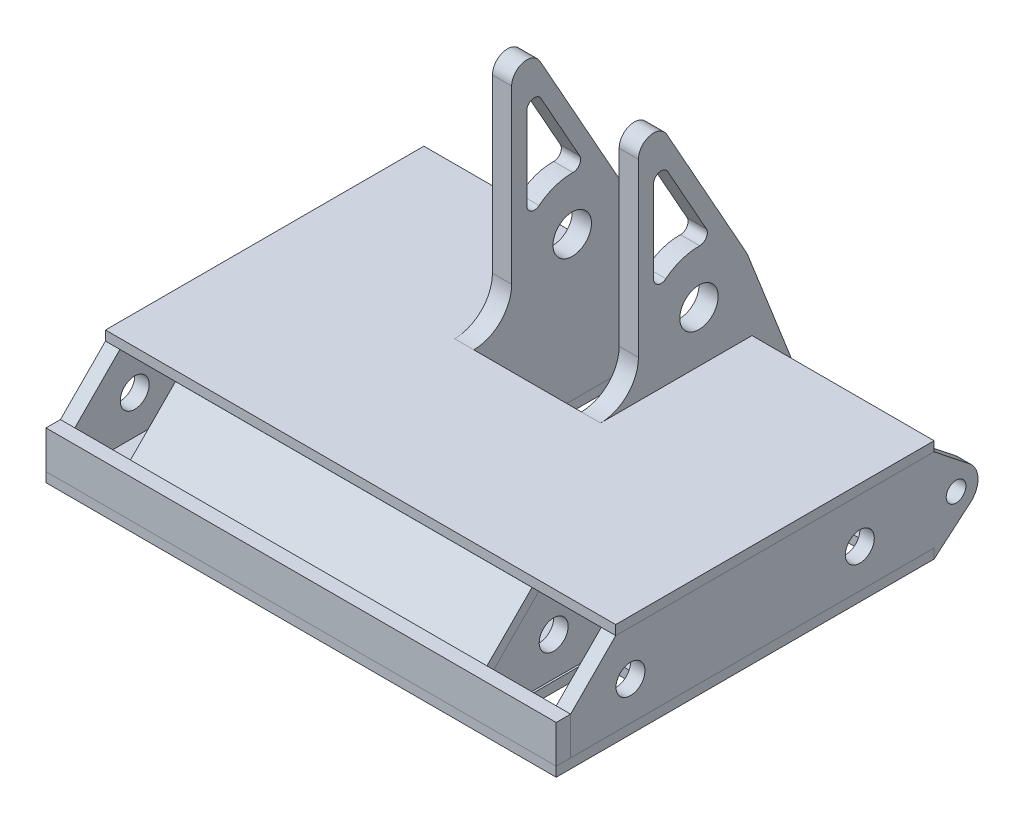
SolidWorks part; units mm, degrees
material "2024-T4"
ref_plane "Front Plane" through (0, 0, 0) normal (0, 0, 1) x (1, 0, 0)
ref_plane "Top Plane" through (0, 0, 0) normal (0, 1, 0) x (1, 0, 0)
ref_plane "Right Plane" through (0, 0, 0) normal (1, 0, 0) x (0, 0, -1)
sketch "Side View" plane through (0, 0, 0) normal (1, 0, 0) x (0, 0, -1)
  line L1 (165, 199.6593) -> (165, 86.35)
  line L3 (140, 55) -> (29.7536, 55)
  line L4 (240, 0) -> (240, 55) construction
  line L5 (0, 0) -> (240, 0)
  line L9 (183.7233, 204.5484) -> (235.5315, 112.1122)
  line L10 (179.9201, 117.2092) -> (110.2141, 38.4935) construction
  line L11 (29.7536, 55) -> (140, 55)
  line L12 (29.7536, 55) -> (29.7536, 61.35) construction
  line L13 (29.7536, 61.35) -> (140, 61.35) construction
  line L14 (140, 55) -> (140, 61.35)
  line L15 (0, 0) -> (240, 0) construction
  line L16 (0, 0) -> (0, -6.35) construction
  line L17 (0, -6.35) -> (240, -6.35) construction
  line L18 (240, 0) -> (240, -6.35) construction
  line L19 (223.5253, 67.0883) -> (135.9217, 8.9446) construction
  line L20 (240, 55) -> (240, 0) construction
  line L21 (240, 0) -> (240, -6.35)
  line L22 (240, 55) -> (230.475, 55) construction
  line L23 (230.475, 55) -> (230.475, 0) construction
  line L24 (13.588, 51.1116) -> (-9.525, 27.8072) construction
  line L25 (240, -6.35) -> (263.8895, 13.9507)
  line L26 (267.9974, 30.2982) -> (237.5799, 107.7886)
  line L27 (13.588, 51.1116) -> (167.8998, 206.7011) construction
  line L28 (190.9625, 41.565) -> (39.5125, 41.565) construction
  line L29 (39.5125, 25.4) -> (190.9625, 25.4) construction
  line L30 (190.9625, 9.235) -> (39.5125, 9.235) construction
  line L31 (-9.525, 25) -> (-9.525, -6.35) construction
  line L32 (-9.525, -6.35) -> (0, -6.35) construction
  line L33 (0, 0) -> (0, 25)
  line L34 (0, 25) -> (29.7536, 55)
  line L35 (-9.525, 25) -> (0, 25) construction
  line L36 (-4.5086, 29.4716) -> (25.245, 59.4716) construction
  line L37 (0, 25) -> (-4.5086, 29.4716) construction
  line L38 (29.7536, 55) -> (25.245, 59.4716) construction
  line L39 (39.701, -11.1125) -> (190.9636, -11.1125) construction
  circle A1 centre (205, 95) radius 12.7
  circle A2 centre (205, 95) radius 100 construction
  arc A3 (183.7233, 204.5484) -> (165, 199.6593) centre (175, 199.6593) ccw
  arc A4 (140, 61.35) -> (165, 86.35) centre (140, 86.35) ccw
  circle A5 centre (125, 25.4) radius 19.75 construction
  circle A6 centre (205, 95) radius 33.5 construction
  circle A7 centre (39.5125, 25.4) radius 36.5125 construction
  circle A8 centre (190.9625, 25.4) radius 36.5125 construction
  circle A9 centre (254.5, 25) radius 6.5
  arc A11 (263.8895, 13.9507) -> (267.9974, 30.2982) centre (254.5, 25) ccw
  arc A13 (237.5799, 107.7886) -> (235.5315, 112.1122) centre (205, 95) ccw
  circle A14 centre (190.9625, 25.4) radius 16.165 construction
  circle A15 centre (39.5125, 25.4) radius 16.165 construction
  point P16 (240, 0)
  point P24 (165, 237.9546)
  point P40 (217.1923, 0)
  point P45 (164.7327, 0)
  point P49 (65.7423, 0)
  point P50 (13.2827, 0)
  dimension "D1" = 25.4
  dimension "D3" = 200
  dimension "D8" = 10
  dimension "D11" = 39.5
  dimension "D15" = 67
  dimension "D17" = 73.025
  dimension "D16" = 13
  dimension "D29" = 73.025
  dimension "D31" = 32.33
  dimension "D32" = 32.33
  dimension "D28" = 35
  dimension "D2" = 55
  dimension "D9" = 6.35
  dimension "D10" = 25
  dimension "D14" = 40
  dimension "D5" = 5
  dimension "D4" = 35
  dimension "D18" = 4.7625
  dimension "D7" = 5
  dimension "D20" = 3
  dimension "D22" = 25
  dimension "D26" = 9.525
  dimension "D13" = 80
  dimension "D19" = 3
  dimension "D6" = 240
  dimension "D24" = 8
  dimension "D25" = 8
  dimension "D27" = 25
  dimension "D30" = 4.7625
  dimension "D34" = 151.45
  dimension "D21" = 6.35
sketch "Top View" plane through (0, 0, 0) normal (0, 1, 0) x (1, 0, 0)
  line L0 (0, 120) -> (0, 0) construction
  line L1 (168.45, 0) -> (158.925, 0)
  line L2 (168.45, 0) -> (168.45, 240)
  line L3 (168.45, 240) -> (35.5, 240)
  line L4 (-168.45, 0) -> (-168.45, 240)
  line L5 (168.45, 0) -> (-168.45, 240) construction
  line L6 (168.45, 240) -> (-168.45, 0) construction
  line L9 (-35.5, 240) -> (-35.5, 0)
  line L11 (35.5, 240) -> (35.5, 0)
  line L13 (-158.925, 230.475) -> (-158.925, 0)
  line L15 (-117.725, 230.475) -> (-117.725, 0)
  line L17 (158.925, 230.475) -> (117.725, 230.475)
  line L18 (158.925, 230.475) -> (158.925, 0)
  line L19 (-35.5, 240) -> (-168.45, 240)
  line L20 (-158.925, 0) -> (-168.45, 0)
  line L22 (158.925, 230.475) -> (48.2, 230.475)
  line L26 (-48.2, 230.475) -> (-158.925, 230.475)
  line L29 (158.925, 0) -> (-108.2, 0)
  line L33 (-131.175, 190.9625) -> (-131.175, 229.0625) construction
  line L35 (-141.335, 77.6125) -> (-141.335, 1.4125) construction
  line L36 (108.2, 165.9625) -> (58.2, 165.9625) construction
  line L37 (-108.2, 215.9625) -> (-58.2, 215.9625) construction
  line L38 (-108.2, 215.9625) -> (-108.2, 165.9625) construction
  line L39 (-108.2, 165.9625) -> (-58.2, 165.9625) construction
  line L40 (-58.2, 215.9625) -> (-58.2, 165.9625) construction
  line L41 (58.2, 215.9625) -> (58.2, 165.9625) construction
  line L42 (108.2, 215.9625) -> (58.2, 215.9625) construction
  line L43 (108.2, 215.9625) -> (108.2, 165.9625) construction
  line L45 (-141.335, 229.0625) -> (-121.015, 229.0625) construction
  line L46 (-141.335, 229.0625) -> (-141.335, 152.8625) construction
  line L47 (-141.335, 152.8625) -> (-121.015, 152.8625) construction
  line L49 (-141.335, 229.0625) -> (-121.015, 152.8625) construction
  line L50 (-141.335, 152.8625) -> (-121.015, 229.0625) construction
  line L54 (-108.2, 240) -> (-108.2, 0) construction
  line L56 (-121.015, 77.6125) -> (-121.015, 1.4125) construction
  line L57 (-48.2, 230.475) -> (-48.2, 0)
  line L58 (48.2, 230.475) -> (48.2, 0)
  line L59 (-108.2, 0) -> (-158.925, 0)
  line L60 (-117.725, 230.475) -> (-117.725, -9.525) construction
  line L61 (105.8641, 240) -> (158.925, 0) construction
  line L62 (-35.5, 240) -> (35.5, 240)
  line L63 (-48.2, 230.475) -> (48.2, 230.475) construction
  line L65 (158.925, 240) -> (105.8641, 240) construction
  line L66 (-158.925, 240) -> (-108.2, 240) construction
  line L67 (-158.925, 230.475) -> (-117.725, 230.475) construction
  line L68 (-141.335, 1.4125) -> (-121.015, 1.4125) construction
  line L69 (-141.335, 39.5125) -> (-155.635, 39.5125) construction
  line L70 (-168.45, 0) -> (-168.45, -9.525)
  line L71 (-141.335, 9.5125) -> (-141.335, 69.5125) construction
  line L72 (-141.335, 160.9625) -> (-155.635, 160.9625) construction
  line L73 (-141.335, 160.9625) -> (-141.335, 220.9625) construction
  line L74 (-141.335, 220.9625) -> (-155.635, 220.9625) construction
  line L75 (-155.635, 160.9625) -> (-155.635, 220.9625) construction
  line L76 (-141.335, 160.9625) -> (-155.635, 220.9625) construction
  line L77 (-141.335, 220.9625) -> (-155.635, 160.9625) construction
  line L78 (-141.335, 9.5125) -> (-155.635, 9.5125) construction
  line L79 (-155.635, 9.5125) -> (-155.635, 69.5125) construction
  line L80 (-141.335, 69.5125) -> (-155.635, 69.5125) construction
  line L81 (-108.2, 230.475) -> (-108.2, 0)
  line L82 (-141.335, 77.6125) -> (-121.015, 77.6125) construction
  line L83 (-141.335, 77.6125) -> (-121.015, 77.6125) construction
  line L84 (-168.45, -9.525) -> (168.45, -9.525)
  line L85 (48.2, 145) -> (117.5, 145) construction
  line L86 (48.2, 145) -> (48.2, 105) construction
  line L87 (48.2, 105) -> (117.5, 105) construction
  line L88 (117.5, 145) -> (117.5, 105) construction
  line L89 (1.5875, 105) -> (-23.8125, 105) construction
  line L90 (1.5875, 105) -> (1.5875, 305) construction
  line L91 (1.5875, 305) -> (-23.8125, 305) construction
  line L92 (-23.8125, 105) -> (-23.8125, 305) construction
  line L93 (1.5875, 105) -> (-23.8125, 305) construction
  line L94 (1.5875, 305) -> (-23.8125, 105) construction
  line L95 (168.45, -9.525) -> (168.45, 0)
  line L96 (0, 105) -> (0, 305) construction
  line L97 (-11.1125, 205) -> (11.1125, 205) construction
  line L98 (20.6375, 171.5) -> (1.5875, 171.5) construction
  line L99 (20.6375, 171.5) -> (20.6375, 238.5) construction
  line L100 (20.6375, 238.5) -> (1.5875, 238.5) construction
  line L101 (1.5875, 171.5) -> (1.5875, 238.5) construction
  line L102 (20.6375, 171.5) -> (1.5875, 238.5) construction
  line L103 (20.6375, 238.5) -> (1.5875, 171.5) construction
  line L104 (170.7859, -9.525) -> (-117.725, -9.525) construction
  line L105 (117.725, 230.475) -> (170.7859, -9.525) construction
  line L106 (141.335, 1.4125) -> (121.015, 1.4125) construction
  line L107 (141.335, 9.5125) -> (155.635, 9.5125) construction
  line L108 (155.635, 9.5125) -> (155.635, 69.5125) construction
  line L109 (108.2, 230.475) -> (108.2, 0)
  line L110 (117.725, 230.475) -> (117.725, 0)
  line L111 (141.335, 69.5125) -> (155.635, 69.5125) construction
  line L112 (141.335, 77.6125) -> (141.335, 1.4125) construction
  line L113 (141.335, 77.6125) -> (121.015, 77.6125) construction
  line L118 (-158.925, 230.475) -> (-158.925, 240)
  line L119 (-48.2, 230.475) -> (-48.2, 240)
  line L120 (48.2, 230.475) -> (48.2, 240)
  line L121 (158.925, 230.475) -> (158.925, 240)
  line L122 (0, 171.5) -> (0, 238.5) construction
  line L123 (-35.5, 145) -> (35.5, 145)
  line L124 (-121.015, 229.0625) -> (-121.015, 152.8625) construction
  line L125 (-107.2, 162) -> (-51.2, 162) construction
  line L126 (-107.2, 162) -> (-107.2, 2) construction
  line L127 (-107.2, 2) -> (-51.2, 2) construction
  line L128 (-51.2, 162) -> (-51.2, 2) construction
  line L129 (-35.5, 104) -> (35.5, 104)
  line L130 (-35.5, 104) -> (-35.5, 94.475)
  line L131 (-35.5, 94.475) -> (35.5, 94.475)
  line L132 (35.5, 104) -> (35.5, 94.475)
  line L133 (121.015, 77.6125) -> (121.015, 1.4125) construction
  line L134 (121.015, 229.0625) -> (121.015, 152.8625) construction
  line L135 (141.335, 152.8625) -> (121.015, 152.8625) construction
  line L136 (141.335, 160.9625) -> (155.635, 160.9625) construction
  line L137 (155.635, 160.9625) -> (155.635, 220.9625) construction
  line L138 (141.335, 220.9625) -> (155.635, 220.9625) construction
  line L139 (141.335, 229.0625) -> (141.335, 152.8625) construction
  line L140 (141.335, 229.0625) -> (121.015, 229.0625) construction
  line L141 (-155.635, 190.9625) -> (-121.015, 190.9625) construction
  line L142 (-158.925, 115.2375) -> (-117.725, 115.2375) construction
  point P0 (0, 0)
  point P44 (-131.175, 190.9625)
  point P45 (-158.925, 115.2375)
  point P55 (-138.325, 115.2375)
  point P58 (-148.485, 190.9625)
  point P60 (-58.2, 190.9625)
  point P76 (0, 205)
  point P77 (11.1125, 205)
  point P78 (-11.1125, 205)
  point P87 (117.5, 125)
  point P133 (-138.325, 190.9625)
  dimension "D5" = 41.2
  dimension "D6" = 9.525
  dimension "D10" = 20.32
  dimension "D11" = 76.2
  dimension "D12" = 50
  dimension "D8" = 9.525
  dimension "D15" = 12.7
  dimension "D7" = 50
  dimension "D4" = 14.3
  dimension "D16" = 60
  dimension "D3" = 71
  dimension "D18" = 9.525
  dimension "D19" = 40
  dimension "D21" = 25.4
  dimension "D22" = 19.05
  dimension "D24" = 9.525
  dimension "D25" = 60
  dimension "D23" = 56
  dimension "D26" = 160
  dimension "D27" = 2
  dimension "D28" = 3
  dimension "D29" = 9.525
  dimension "D30" = 1
  dimension "D31" = 60
  dimension "D32" = 336.9
  dimension "D20" = 82
  dimension "D33" = 240
  dimension "D9" = 9.525
  dimension "D13" = 2
  dimension "D17" = 2
ref_plane "Left Weapon Wall Plane" through (-35.5, 0, 0) normal (1, 0, 0) x (0, 0, -1)
ref_plane "Right Weapon Wall Plane" through (35.5, 0, 0) normal (1, 0, 0) x (0, 0, -1)
ref_plane "Front Wall Plane" through (0, 0, -240) normal (0, 0, 1) x (1, 0, 0)
ref_plane "Rear Wall Plane" through (0, 0, 9.525) normal (0, 0, 1) x (1, 0, 0)
ref_plane "Left Motor Wall Plane" through (-108.2, 0, 0) normal (1, 0, 0) x (0, 0, -1)
ref_plane "Right Motor Wall Plane" through (108.2, 0, 0) normal (1, 0, 0) x (0, 0, -1)
ref_plane "Left Outside Wall Plane" through (-168.45, 0, 0) normal (1, 0, 0) x (0, 0, -1)
ref_plane "Wheel Center" through (-131.175, 0, 0) normal (1, 0, 0) x (0, 0, -1)
ref_plane "Angled Back Plane" through (0, 12.3969, 12.4996) normal (0, -0.7042, -0.71) x (0, 0.71, -0.7042)
ref_plane "Top Plate Plane" through (0, 55, 0) normal (0, 1, 0) x (1, 0, 0)
ref_plane "Shielding Plate Plane" through (0, 0, -104) normal (0, 0, 1) x (1, 0, 0)
sketch "Sketch14" plane through (0, 0, -104) normal (0, 0, 1) x (1, 0, 0)
  line L1 (-35.5, 0) -> (35.5, 0)
  line L2 (-35.5, 0) -> (-35.5, 55)
  line L3 (-35.5, 55) -> (35.5, 55)
  line L4 (35.5, 0) -> (35.5, 55)
extrude "Boss-Extrude9" add sketch "Sketch14" along normal up to vertex (9.525 mm away) up to point (-35.5, 0, -94.475)
sketch "Sketch2" plane through (0, 0, 0) normal (0, 1, 0) x (1, 0, 0)
  line L0 (168.45, -9.525) -> (168.45, 0) construction
  line L1 (-168.45, 0) -> (-168.45, -9.525) construction
  line L2 (-168.45, -9.525) -> (168.45, -9.525) construction
  line L3 (168.45, 0) -> (168.45, 240) construction
  line L4 (168.45, 240) -> (35.5, 240) construction
  line L5 (35.5, 240) -> (35.5, 0) construction
  line L6 (-35.5, 145) -> (35.5, 145) construction
  line L7 (-35.5, 240) -> (-35.5, 0) construction
  line L8 (-35.5, 240) -> (-168.45, 240) construction
  line L9 (-168.45, 0) -> (-168.45, 240) construction
  line L10 (168.45, -9.525) -> (168.45, 0)
  line L11 (-168.45, 0) -> (-168.45, -9.525)
  line L12 (-168.45, -9.525) -> (168.45, -9.525)
  line L13 (168.45, 0) -> (168.45, 240)
  line L14 (168.45, 240) -> (35.5, 240)
  line L15 (35.5, 240) -> (35.5, 145)
  line L16 (-35.5, 145) -> (35.5, 145)
  line L17 (-35.5, 240) -> (-35.5, 145)
  line L18 (-35.5, 240) -> (-168.45, 240)
  line L19 (-168.45, 0) -> (-168.45, 240)
  line L20 (-143.335, 9.5125) -> (-143.335, 69.5125)
  line L21 (-119.015, 69.5125) -> (-143.335, 69.5125)
  line L22 (-119.015, 9.5125) -> (-119.015, 69.5125)
  line L23 (-119.015, 9.5125) -> (-143.335, 9.5125)
  line L24 (-141.335, 39.5125) -> (-155.635, 39.5125) construction
  line L27 (0, 145) -> (0, 0) construction
  line L45 (119.015, 160.9625) -> (119.015, 220.9625)
  line L46 (119.015, 220.9625) -> (143.335, 220.9625)
  line L47 (143.335, 160.9625) -> (143.335, 220.9625)
  line L48 (119.015, 160.9625) -> (143.335, 160.9625)
  line L53 (-121.015, 229.0625) -> (-121.015, 152.8625) construction
  line L54 (-119.015, 160.9625) -> (-143.335, 160.9625)
  line L55 (-119.015, 160.9625) -> (-119.015, 220.9625)
  line L56 (-119.015, 220.9625) -> (-143.335, 220.9625)
  line L57 (-143.335, 160.9625) -> (-143.335, 220.9625)
  line L58 (-119.015, 160.9625) -> (-143.335, 220.9625) construction
  line L59 (-119.015, 220.9625) -> (-143.335, 160.9625) construction
  line L60 (119.015, 9.5125) -> (119.015, 69.5125)
  line L61 (119.015, 9.5125) -> (143.335, 9.5125)
  line L62 (143.335, 9.5125) -> (143.335, 69.5125)
  line L63 (119.015, 69.5125) -> (143.335, 69.5125)
  point P6 (-131.175, 190.9625)
  point P8 (-143.335, 39.5125)
  dimension "D1" = 2
  dimension "D2" = 60
  dimension "D3" = 2
extrude "Bottom Plate" add sketch "Sketch2" against normal up to vertex (6.35 mm away) up to point (0, -6.35, 0)
sketch "Sketch3" plane through (-35.5, 0, 0) normal (1, 0, 0) x (0, 0, -1)
  line L0 (140, 55) -> (29.7536, 55) construction
  line L2 (140, 55) -> (140, 61.35) construction
  line L3 (165, 199.6593) -> (165, 86.35) construction
  line L4 (183.7233, 204.5484) -> (235.5315, 112.1122) construction
  line L7 (0, 0) -> (240, 0) construction
  line L8 (0, 0) -> (0, 25) construction
  line L9 (0, 25) -> (29.7536, 55) construction
  line L10 (140, 55) -> (29.7536, 55)
  line L12 (140, 55) -> (140, 61.35)
  line L13 (165, 199.6593) -> (165, 86.35)
  line L14 (183.7233, 204.5484) -> (235.5315, 112.1122)
  line L17 (0, 0) -> (240, 0)
  line L18 (0, 0) -> (0, 25)
  line L19 (0, 25) -> (29.7536, 55)
  line L20 (240, 0) -> (240, -6.35) construction
  line L21 (240, -6.35) -> (263.8895, 13.9507) construction
  line L22 (267.9974, 30.2982) -> (237.5799, 107.7886) construction
  line L23 (240, 0) -> (240, -6.35)
  line L24 (240, -6.35) -> (263.8895, 13.9507)
  line L25 (267.9974, 30.2982) -> (237.5799, 107.7886)
  line L26 (175, 199.6593) -> (214.8322, 128.5906)
  line L27 (175, 199.6593) -> (175, 113.0278)
  line L28 (175, 199.6593) -> (226.8082, 107.223) construction
  line L29 (175, 199.6593) -> (175, 86.35) construction
  arc A0 (140, 61.35) -> (165, 86.35) centre (140, 86.35) ccw construction
  arc A1 (183.7233, 204.5484) -> (165, 199.6593) centre (175, 199.6593) ccw construction
  arc A3 (140, 61.35) -> (165, 86.35) centre (140, 86.35) ccw
  arc A4 (183.7233, 204.5484) -> (165, 199.6593) centre (175, 199.6593) ccw
  circle A6 centre (205, 95) radius 12.7 construction
  circle A7 centre (205, 95) radius 12.7
  arc A8 (263.8895, 13.9507) -> (267.9974, 30.2982) centre (254.5, 25) ccw construction
  arc A9 (263.8895, 13.9507) -> (267.9974, 30.2982) centre (254.5, 25) ccw
  arc A12 (237.5799, 107.7886) -> (235.5315, 112.1122) centre (205, 95) ccw construction
  arc A13 (237.5799, 107.7886) -> (235.5315, 112.1122) centre (205, 95) ccw
  circle A14 centre (254.5, 25) radius 6.5 construction
  circle A15 centre (254.5, 25) radius 6.5
  arc A16 (214.8322, 128.5906) -> (175, 113.0278) centre (205, 95) ccw
  dimension "D3" = 35
  dimension "D1" = 10
  dimension "D2" = 10
extrude "Left Weapon Wall" add sketch "Sketch3" against normal up to vertex (12.7 mm away) separate body contours L14 A4 L13 A3 L12 L10 L19 L18 L17 A7 region at (-35.5, 53.8293, -156.1173) up to point (-48.2, 0, 0)
fillet "Fillet1" radius 5 3 edges at (-41.85, 199.6593, -175) (-41.85, 113.0278, -175) (-41.85, 128.5906, -214.8322)
sketch "Sketch5" plane through (-168.45, 0, 0) normal (1, 0, 0) x (0, 0, -1)
  line L1 (0, 0) -> (240, 0) construction
  line L2 (0, 0) -> (0, 25) construction
  line L3 (0, 25) -> (29.7536, 55) construction
  line L4 (140, 55) -> (29.7536, 55) construction
  line L6 (0, 0) -> (240, 0)
  line L7 (0, 0) -> (0, 25)
  line L8 (0, 25) -> (29.7536, 55)
  line L9 (240, 55) -> (29.7536, 55)
  line L10 (240, -6.35) -> (263.8895, 13.9507) construction
  line L11 (240, 0) -> (240, -6.35) construction
  line L12 (240, -6.35) -> (263.8895, 13.9507)
  line L13 (240, 0) -> (240, -6.35)
  line L14 (263.5082, 36.3623) -> (240, 55)
  line L15 (240, 55) -> (230.475, 55) construction
  arc A0 (263.8895, 13.9507) -> (267.9974, 30.2982) centre (254.5, 25) ccw construction
  arc A1 (263.8895, 13.9507) -> (263.5082, 36.3623) centre (254.5, 25) ccw
  circle A2 centre (254.5, 25) radius 6.5 construction
  circle A3 centre (254.5, 25) radius 6.5
  point P6 (39.5125, 25.4)
  point P8 (190.9625, 25.4)
extrude "Left Wall" add sketch "Sketch5" along normal up to vertex (9.525 mm away) separate body up to point (-158.925, 0, 0)
sketch "Sketch6" plane through (-108.2, 0, 0) normal (1, 0, 0) x (0, 0, -1)
  line L1 (240, 0) -> (-9.525, 0) construction
  line L2 (0, 0) -> (0, 25) construction
  line L3 (0, 25) -> (29.7536, 55) construction
  line L4 (140, 55) -> (29.7536, 55) construction
  line L6 (230.475, 0) -> (0, 0)
  line L7 (0, 0) -> (0, 25)
  line L8 (0, 25) -> (29.7536, 55)
  line L9 (230.475, 55) -> (29.7536, 55)
  line L10 (230.475, 55) -> (230.475, 0) construction
  line L11 (230.475, 55) -> (230.475, 0)
extrude "Left Motor Wall" add sketch "Sketch6" against normal up to vertex (9.525 mm away) separate body up to point (-117.725, 0, 0)
sketch "Sketch7" plane through (0, 0, 9.525) normal (0, 0, 1) x (1, 0, 0)
  line L1 (-168.45, 0) -> (168.45, 0) construction
  line L2 (-168.45, 0) -> (168.45, 0)
  line L4 (-168.45, 0) -> (168.45, 0)
  line L5 (-168.45, 0) -> (-168.45, 25)
  line L6 (-168.45, 25) -> (168.45, 25)
  line L7 (168.45, 0) -> (168.45, 25)
  point P0 (0, 25)
extrude "Rear Wall" add sketch "Sketch7" against normal up to vertex (9.525 mm away) separate body contours L2 L7 L6 L5 region at (0, 12.5, 9.525) up to point (0, 0, 0)
sketch "Sketch8" plane through (0, 0, -240) normal (0, 0, 1) x (1, 0, 0)
  line L0 (-35.5, 0) -> (-168.45, 0) construction
  line L1 (-48.2, 0) -> (-158.925, 0)
  line L3 (-48.2, 0) -> (-158.925, 0)
  line L5 (-48.2, 55) -> (-158.925, 55)
  line L8 (-48.2, 55) -> (-48.2, 0)
  line L9 (-158.925, 0) -> (-158.925, 55)
  point P0 (0, 55)
  point P10 (-158.925, 0)
extrude "Boss-Extrude6" add sketch "Sketch8" along normal up to vertex (9.525 mm away) separate body contours L1 L5 region at (-103.5625, 27.5, -240) up to point (-48.2, 0, -230.475)
mirror "Mirror1" about plane through (0, 0, 0) normal (1, 0, 0) of bodies 103 106 102 104
sketch "Sketch10" plane through (108.2, 0, 0) normal (-1, 0, 0) x (0, 0, 1)
  circle A0 centre (-190.9625, 25.4) radius 5
  circle A1 centre (-39.5125, 25.4) radius 9.55
  circle A2 centre (-125, 25.4) radius 20.5
  dimension "D1" = 10
  dimension "D2" = 41
  dimension "D3" = 19.1
extrude "Cut-Extrude1" cut sketch "Sketch10" against normal up to next (9.525 mm away)
sketch "Sketch11" plane through (-117.725, 0, 0) normal (-1, 0, 0) x (0, 0, 1)
  circle A0 centre (-39.5125, 25.4) radius 9.55 construction
  circle A1 centre (-190.9625, 25.4) radius 5 construction
  circle A2 centre (-39.5125, 25.4) radius 9.55
  circle A3 centre (-190.9625, 25.4) radius 5
extrude "Cut-Extrude2" cut sketch "Sketch11" against normal up to next (9.525 mm away)
sketch "Sketch12" plane through (0, 12.3969, 12.4996) normal (0, -0.7042, -0.71) x (0, 0.71, -0.7042)
  line L0 (162.2971, -117.725) -> (0, -117.725) construction
  line L1 (60.003, 117.725) -> (17.7504, 117.725)
  line L2 (60.003, 117.725) -> (60.003, -117.725)
  line L3 (60.003, -117.725) -> (17.7504, -117.725)
  line L4 (17.7504, 117.725) -> (17.7504, -117.725)
  line L8 (0, 0) -> (60.003, 0) construction
  line L9 (-4.5086, 0) -> (164.4959, 0) construction
  dimension "D1" = 0
extrude "Rear Angled Plate" add sketch "Sketch12" against normal up to vertex (6.35 mm away) separate body up to point (0, 59.4716, -25.245)
sketch "Sketch13" plane through (0, 55, 0) normal (0, 1, 0) x (1, 0, 0)
  line L25 (0, 140) -> (0, 29.7536) construction
  line L26 (-48.2, 230.475) -> (-48.2, 0) construction
  line L27 (-48.2, 230.475) -> (-48.2, 240) construction
  line L28 (-35.5, 240) -> (-168.45, 240) construction
  line L29 (-168.45, 0) -> (-168.45, 240) construction
  line L31 (168.45, 29.7536) -> (168.45, 240)
  line L33 (48.2, 240) -> (168.45, 240)
  line L34 (0, 140) -> (0, 29.7536) construction
  line L35 (-48.2, 230.475) -> (-48.2, 140)
  line L36 (-48.2, 230.475) -> (-48.2, 240)
  line L37 (-48.2, 240) -> (-168.45, 240)
  line L38 (-168.45, 29.7536) -> (-168.45, 240)
  line L40 (-48.2, 140) -> (48.2, 140)
  line L43 (-168.45, 29.7536) -> (168.45, 29.7536)
  line L44 (48.2, 230.475) -> (48.2, 240)
  line L45 (48.2, 230.475) -> (48.2, 140)
  line L50 (-117.725, 29.7536) -> (117.725, 29.7536) construction
extrude "Top Plate" add sketch "Sketch13" along normal up to vertex (6.35 mm away) separate body up to point (0, 61.35, -29.7536)
sketch "Sketch15" plane through (48.2, 0, 0) normal (1, 0, 0) x (0, 0, -1)
  circle A0 centre (125, 25.4) radius 19.75 construction
  circle A1 centre (125, 25.4) radius 19.75 construction
  circle A2 centre (125, 25.4) radius 20.5
  dimension "D1" = 41
extrude "Cut-Extrude3" cut sketch "Sketch15" against normal up to surface (12.7 mm away) up to face at (35.5, 25, -261)
sketch "Sketch16" plane through (-168.45, 0, 0) normal (1, 0, 0) x (0, 0, -1)
  circle A0 centre (39.5125, 25.4) radius 9.55 construction
  circle A1 centre (39.5125, 25.4) radius 9.55
  circle A2 centre (190.9625, 25.4) radius 9.55
extrude "Cut-Extrude4" cut sketch "Sketch16" along normal up to next (9.525 mm away)
mirror "Mirror3" about plane through (0, 0, 0) normal (1, 0, 0) of "Cut-Extrude4"
equation "\"D8@Top View\"=\"D9@Top View\""
equation "\"D18@Top View\"=\"D8@Top View\""
equation "\"D24@Top View\"=\"D8@Top View\""
equation "\"D19@Side View\"=\"D20@Side View\""
equation "\"D29@Top View\"=\"D18@Top View\""
equation "\"D30@Side View\"=\"D18@Side View\""
equation "\"D31@Side View\"=\"D32@Side View\""
equation "\"D2@Sketch3\"=\"D1@Sketch3\""
